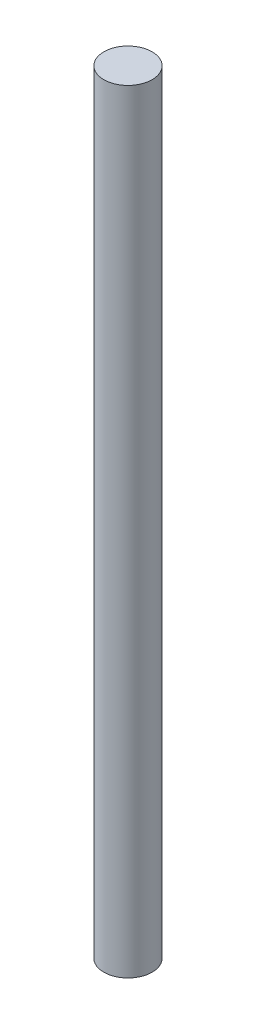
SolidWorks part; units mm, degrees
ref_plane "Спереди" through (0, 0, 0) normal (0, 0, 1) x (1, 0, 0)
ref_plane "Сверху" through (0, 0, 0) normal (0, 1, 0) x (1, 0, 0)
ref_plane "Справа" through (0, 0, 0) normal (1, 0, 0) x (0, 0, -1)
sketch "Sketch1" plane through (0, 0, 0) normal (0, 1, 0) x (1, 0, 0)
  circle A0 centre (0, 0) radius 3
  dimension "D1" = 6
extrude "Boss-Extrude1" add sketch "Sketch1" along normal blind 96
